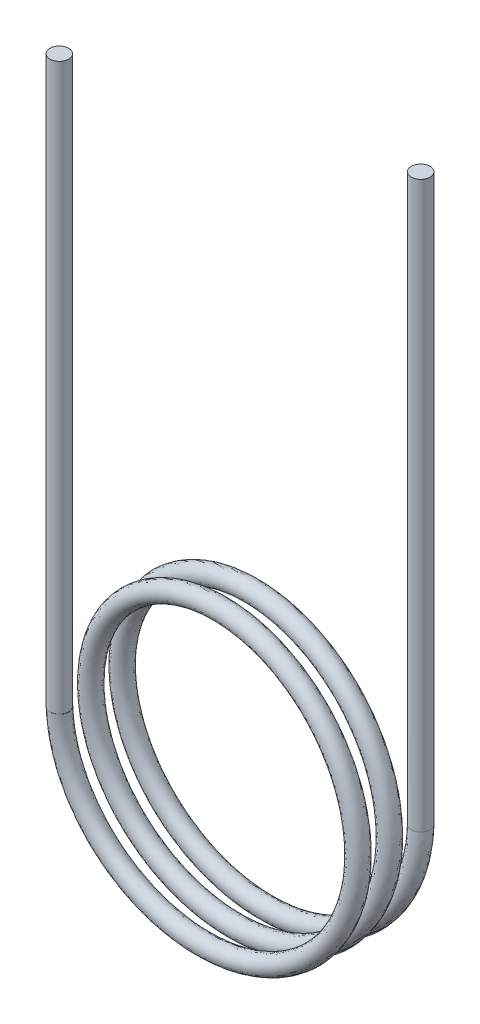
SolidWorks part; units mm, degrees
ref_plane "Plano frontal" through (0, 0, 0) normal (0, 0, 1) x (1, 0, 0)
ref_plane "Plano superior" through (0, 0, 0) normal (0, 1, 0) x (1, 0, 0)
ref_plane "Plano direito" through (0, 0, 0) normal (1, 0, 0) x (0, 0, -1)
sketch "Esboço1" plane through (0, 0, 0) normal (0, 0, 1) x (1, 0, 0)
  circle A0 centre (0, 0) radius 22.5
  dimension "D1" = 45
curve "Hélice/Espiral2" pitch 5 height 12.5 radius 22.5 left hand yes centre (0, 0, 0) axis (0, 0, 1) start towards (1, 0, 0)
sketch "Esboço2" plane through (0, 0, 0) normal (0, 1, 0) x (1, 0, 0)
  circle A0 centre (22.5, 0) radius 1.5
  spline S0 degree 3 poles (22.5, 0) (22.5, -0.0798) (21.8104, -0.2405) (18.8009, -0.4807) (14.0888, -0.7212) (8.1009, -0.9615) (1.3793, -1.2019) (-5.4671, -1.4423) (-11.8185, -1.6827) (-17.0996, -1.9231) (-20.8322, -2.1635) (-22.6782, -2.4038) (-22.4706, -2.6442) (-20.2281, -2.8846) (-16.1537, -3.125) (-10.6165, -3.3654) (-4.1179, -3.6058) (2.7536, -3.8462) (9.3758, -4.0865) (15.1489, -4.3269) (19.5501, -4.5673) (22.181, -4.8077) (22.8031, -5.0481) (21.3603, -5.2885) (17.983, -5.5288) (12.9773, -5.7692) (6.7964, -6.0096) (0, -6.25) (-6.7964, -6.4904) (-12.9773, -6.7308) (-17.983, -6.9712) (-21.3603, -7.2115) (-22.8031, -7.4519) (-22.181, -7.6923) (-19.5501, -7.9327) (-15.1489, -8.1731) (-9.3758, -8.4135) (-2.7536, -8.6538) (4.1179, -8.8942) (10.6165, -9.1346) (16.1537, -9.375) (20.2281, -9.6154) (22.4706, -9.8558) (22.6782, -10.0962) (20.8322, -10.3365) (17.0996, -10.5769) (11.8185, -10.8173) (5.4671, -11.0577) (-1.3793, -11.2981) (-8.1009, -11.5385) (-14.0888, -11.7788) (-18.8009, -12.0193) (-21.8104, -12.2595) (-22.5, -12.4202) (-22.5, -12.5) knots 0 0 0 0 0.019231 0.038462 0.057692 0.076923 0.096154 0.115385 0.134615 0.153846 0.173077 0.192308 0.211538 0.230769 0.25 0.269231 0.288462 0.307692 0.326923 0.346154 0.365385 0.384615 0.403846 0.423077 0.442308 0.461538 0.480769 0.5 0.519231 0.538462 0.557692 0.576923 0.596154 0.615385 0.634615 0.653846 0.673077 0.692308 0.711538 0.730769 0.75 0.769231 0.788462 0.807692 0.826923 0.846154 0.865385 0.884615 0.903846 0.923077 0.942308 0.961538 0.980769 1 1 1 1 construction
  dimension "D1" = 3
sweep "Varredura1" add profiles "Esboço2" path "Hélice/Espiral2"
extrude "Ressalto-extrusão3" add sketch "Esboço2<2>" along normal blind 90
sketch "Esboço2<2>" plane through (0, 0, 0) normal (0, 1, 0) x (1, 0, 0) same geometry as "Esboço2"
sketch "Esboço8" plane through (0, 0, 0) normal (0, 1, 0) x (1, 0, 0)
  circle A1 centre (-22.5372, -12.5) radius 1.5
  dimension "D1" = 3
extrude "Ressalto-extrusão5" add sketch "Esboço8" along normal blind 90
equation "\"diam_interno\"=45"
equation "\"diam_tubo\"=3"
equation "\"D1@Esboço2\"=\"diam_tubo\""
